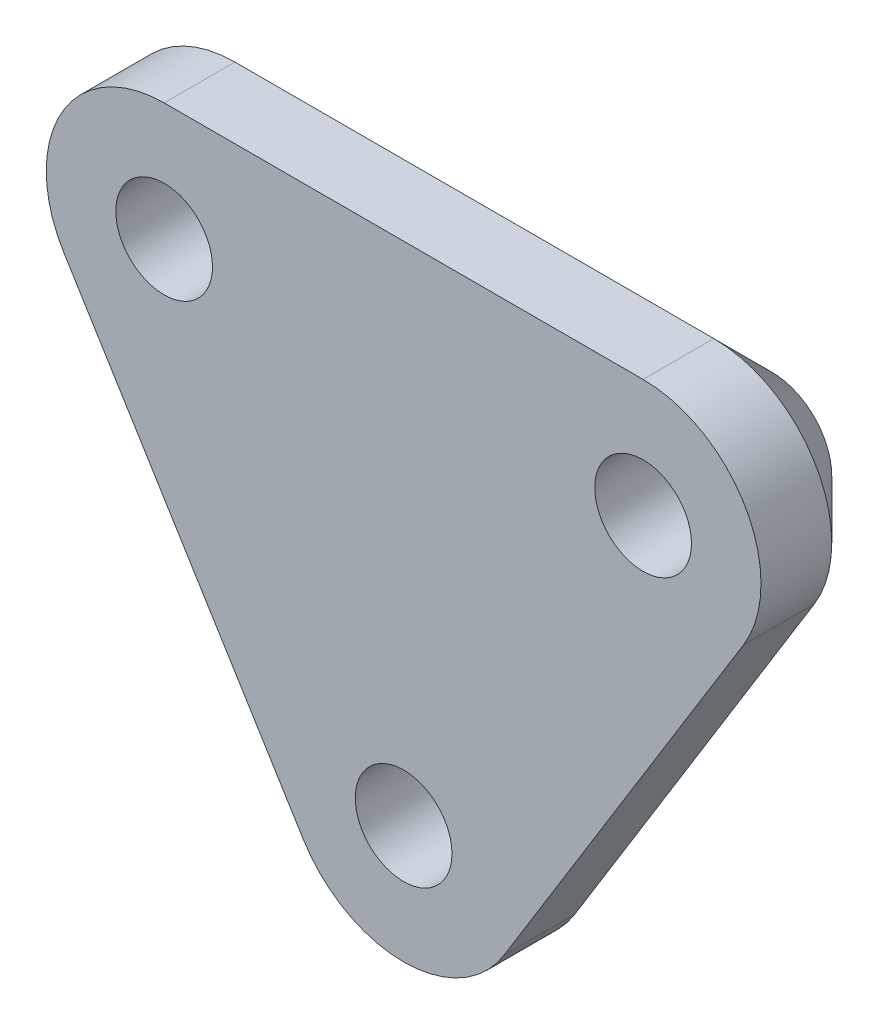
SolidWorks part; units mm, degrees
ref_plane "Front Plane" through (0, 0, 0) normal (0, 0, 1) x (1, 0, 0)
ref_plane "Top Plane" through (0, 0, 0) normal (0, 1, 0) x (1, 0, 0)
ref_plane "Right Plane" through (0, 0, 0) normal (1, 0, 0) x (0, 0, -1)
sketch "Sketch1" plane through (0, 0, 0) normal (0, 0, 1) x (1, 0, 0)
  line L0 (-14.411, 13.8458) -> (-4.256, -2.6242)
  line L1 (4.256, -2.6242) -> (14.411, 13.8458)
  line L2 (10.155, 21.47) -> (-10.155, 21.47)
  line L3 (0, 0) -> (0, 21.47) construction
  arc A0 (-4.256, -2.6242) -> (4.256, -2.6242) centre (0, 0) ccw
  arc A1 (-10.155, 21.47) -> (-14.411, 13.8458) centre (-10.155, 16.47) ccw
  arc A2 (14.411, 13.8458) -> (10.155, 21.47) centre (10.155, 16.47) ccw
  circle A3 centre (-10.155, 16.47) radius 2.05
  circle A4 centre (10.155, 16.47) radius 2.05
  circle A5 centre (0, 0) radius 2.05
  point P1 (-12.336, 21.47)
  point P4 (0, 0)
  point P17 (-13.4117, 10.469)
  dimension "D1" = 4.1
  dimension "D2" = 10
  dimension "D3" = 16.47
  dimension "D4" = 20.31
extrude "Boss-Extrude1" add sketch "Sketch1" along normal blind 3
sketch "Sketch2" plane through (0, 0, 0) normal (0, 0, -1) x (-1, 0, 0)
  circle A0 centre (0, 0) radius 2.05
  circle A1 centre (0, 0) radius 5
  circle A2 centre (10.155, 16.47) radius 2.05
  circle A3 centre (10.155, 16.47) radius 5
  circle A4 centre (-10.155, 16.47) radius 2.05
  circle A5 centre (-10.155, 16.47) radius 5
  arc A6 (-4.256, -2.6242) -> (4.256, -2.6242) centre (0, 0) ccw construction
  circle A7 centre (0, 0) radius 2.05 construction
  point P13 (-10.155, 16.47)
  point P14 (-9.9906, 16.47)
  dimension "D1" = 2.95
extrude "Boss-Extrude2" add sketch "Sketch2" along normal blind 2.95
chamfer "Chamfer1" distance 2.95 angle 45 3 edges at (-5, 0, -2.95) (-15.155, 16.47, -2.95) (5.155, 16.47, -2.95)
ref_plane "Plane1" through (0, 0, -2.95) normal (0, 0, 1) x (1, 0, 0)
sketch "Sketch3" plane through (0, 0, -2.95) normal (0, 0, 1) x (1, 0, 0)
  line L1 (-18.6772, 22.3421) -> (19.1761, 22.3421)
  line L2 (-18.6772, 22.3421) -> (-18.6772, -6.4164)
  line L3 (-18.6772, -6.4164) -> (19.1761, -6.4164)
  line L4 (19.1761, 22.3421) -> (19.1761, -6.4164)
extrude "Cut-Extrude1" cut sketch "Sketch3" along normal blind 0.5
